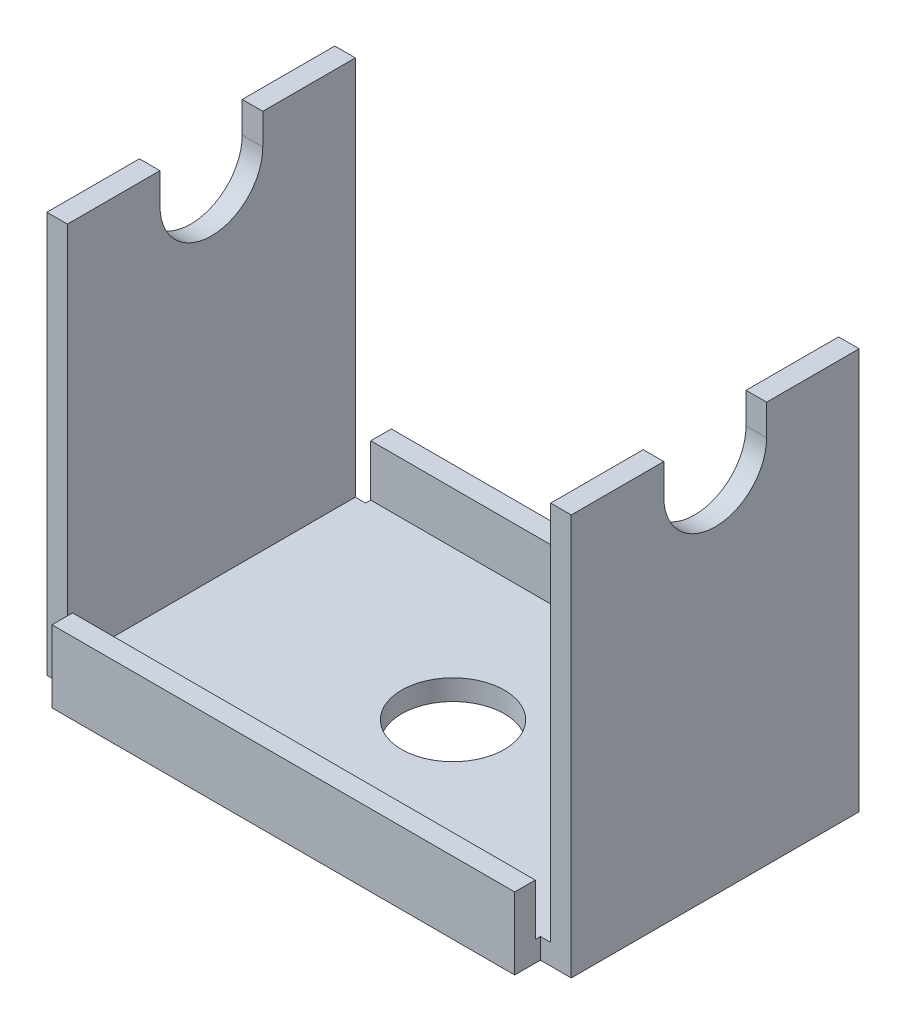
SolidWorks part; units mm, degrees
ref_plane "Front Plane" through (0, 0, 0) normal (0, 0, 1) x (1, 0, 0)
ref_plane "Top Plane" through (0, 0, 0) normal (0, 1, 0) x (1, 0, 0)
ref_plane "Right Plane" through (0, 0, 0) normal (1, 0, 0) x (0, 0, -1)
sketch "Sketch1" plane through (0, 0, 0) normal (0, 0, 1) x (1, 0, 0)
  line L0 (-25.5, 3) -> (-25.5, -36)
  line L1 (-25.5, -36) -> (25.5, -36)
  line L2 (25.5, -36) -> (25.5, 3)
  line L3 (25.5, 3) -> (23.5, 3)
  line L4 (23.5, 3) -> (23.5, -34)
  line L5 (23.5, -34) -> (-23.5, -34)
  line L6 (-23.5, -34) -> (-23.5, 3)
  line L7 (-23.5, 3) -> (-25.5, 3)
  dimension "D1" = 3
  dimension "D2" = 51
  dimension "D3" = 2
  dimension "D4" = 39
  dimension "D5" = 2
  dimension "D6" = 23.5
extrude "Boss-Extrude1" add sketch "Sketch1" against normal mid plane 28
sketch "Sketch2" plane through (0, 0, 0) normal (1, 0, 0) x (0, 0, -1)
  line L0 (-14, -36) -> (-16.5, -36)
  line L1 (14, -36) -> (-14, -36) construction
  line L2 (-16.5, -36) -> (-16.5, -29)
  line L3 (-16.5, -29) -> (-14.5, -29)
  line L4 (-14.5, -29) -> (-14.5, -34)
  line L5 (-14.5, -34) -> (-14, -34)
  line L6 (-14, -34) -> (-14, -36)
  dimension "D1" = 2
  dimension "D2" = 0.5
  dimension "D3" = 7
extrude "Boss-Extrude2" add sketch "Sketch2" along normal mid plane 45
mirror "Mirror1" about plane through (0, 0, 0) normal (0, 0, 1) of "Boss-Extrude2"
sketch "Sketch3" plane through (25.5, 0, 0) normal (1, 0, 0) x (0, 0, -1)
  line L0 (14, -36) -> (-14, -36) construction
  line L1 (-5, 0) -> (-5, 3)
  line L2 (14, 3) -> (-14, 3) construction
  line L3 (5, 0) -> (5, 3)
  line L4 (0, -36) -> (0, 0) construction
  line L5 (-5, 3) -> (5, 3)
  arc A0 (-5, 0) -> (5, 0) centre (0, 0) ccw
  dimension "D1" = 10
  dimension "D2" = 36
extrude "Cut-Extrude1" cut sketch "Sketch3" against normal through all
sketch "Sketch4" plane through (0, -34, 0) normal (0, 1, 0) x (1, 0, 0)
  line L0 (0, 0) -> (-23.5, 0) construction
  line L1 (-23.5, -5) -> (-23.5, 5) construction
  line L2 (-23.5, 14) -> (-23.5, -14) construction
  circle A0 centre (0, 0) radius 5
  dimension "D1" = 10
extrude "Cut-Extrude2" cut sketch "Sketch4" against normal through all
equation "\"D1@Sketch1\" = 39-36"
